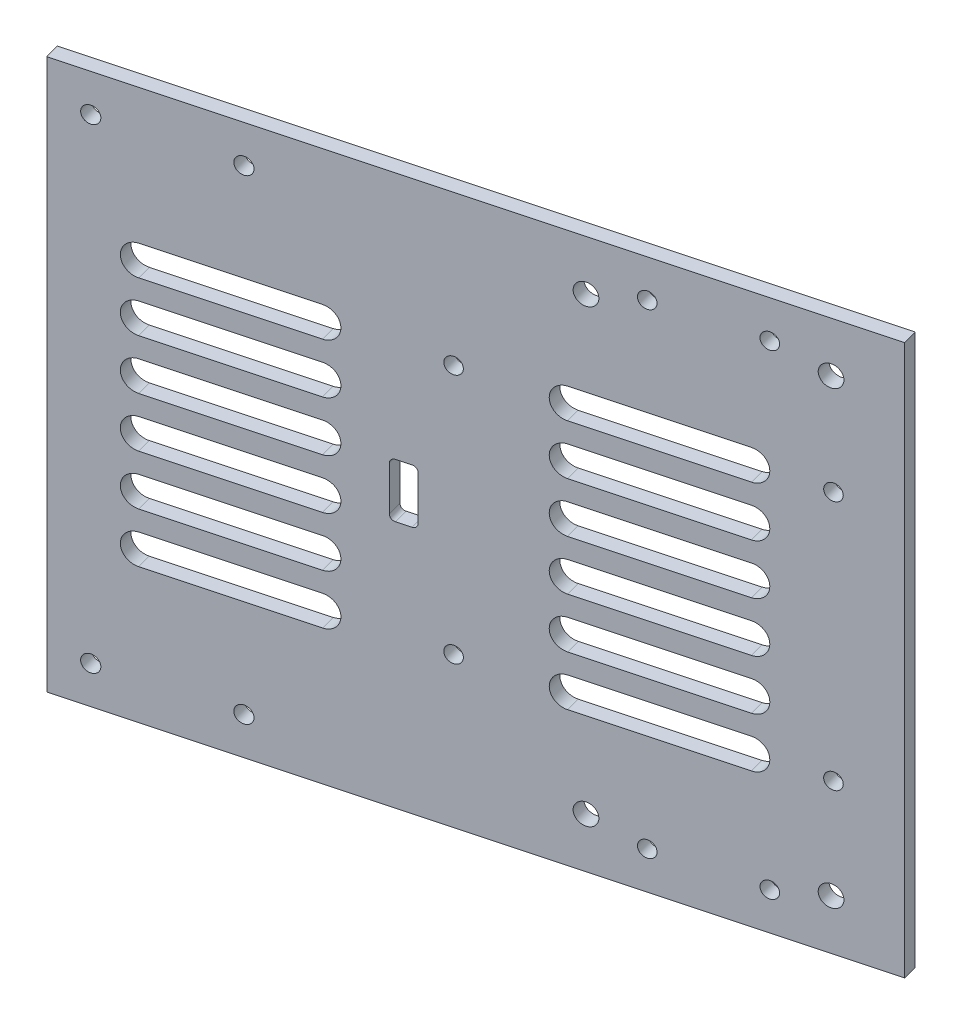
SolidWorks part; units mm, degrees
ref_plane "前视基准面" through (0, 0, 0) normal (0, 0, 1) x (1, 0, 0)
ref_plane "上视基准面" through (0, 0, 0) normal (0, 1, 0) x (1, 0, 0)
ref_plane "右视基准面" through (0, 0, 0) normal (1, 0, 0) x (0, 0, -1)
sketch "Sketch2" plane through (-8.5359, 0, -31.8565) normal (0.2588, 0, 0.9659) x (0.9659, 0, -0.2588)
  line L0 (48.5195, 100.0044) -> (48.5195, -9.9956)
  line L1 (48.5195, -9.9956) -> (188.5195, -9.9956)
  line L2 (188.5195, -9.9956) -> (188.5195, 100.0044)
  line L3 (188.5195, 100.0044) -> (48.5195, 100.0044)
  arc A4 (54.0432, -2.4956) -> (57.3432, -2.4956) centre (55.6932, -2.4956) ccw construction
  arc A5 (57.3432, -2.4956) -> (54.0432, -2.4956) centre (55.6932, -2.4956) ccw construction
  arc A6 (79.0432, -2.4956) -> (82.3432, -2.4956) centre (80.6932, -2.4956) ccw construction
  arc A7 (82.3432, -2.4956) -> (79.0432, -2.4956) centre (80.6932, -2.4956) ccw construction
  arc A8 (79.0432, 92.5044) -> (82.3432, 92.5044) centre (80.6932, 92.5044) ccw construction
  arc A9 (82.3432, 92.5044) -> (79.0432, 92.5044) centre (80.6932, 92.5044) ccw construction
  arc A10 (54.0432, 92.5044) -> (57.3432, 92.5044) centre (55.6932, 92.5044) ccw construction
  arc A11 (57.3432, 92.5044) -> (54.0432, 92.5044) centre (55.6932, 92.5044) ccw construction
  arc A12 (54.0432, -2.4956) -> (57.3432, -2.4956) centre (55.6932, -2.4956) ccw
  arc A13 (57.3432, -2.4956) -> (54.0432, -2.4956) centre (55.6932, -2.4956) ccw
  arc A14 (79.0432, -2.4956) -> (82.3432, -2.4956) centre (80.6932, -2.4956) ccw
  arc A15 (82.3432, -2.4956) -> (79.0432, -2.4956) centre (80.6932, -2.4956) ccw
  arc A16 (79.0432, 92.5044) -> (82.3432, 92.5044) centre (80.6932, 92.5044) ccw
  arc A17 (82.3432, 92.5044) -> (79.0432, 92.5044) centre (80.6932, 92.5044) ccw
  arc A18 (54.0432, 92.5044) -> (57.3432, 92.5044) centre (55.6932, 92.5044) ccw
  arc A19 (57.3432, 92.5044) -> (54.0432, 92.5044) centre (55.6932, 92.5044) ccw
  circle A20 centre (166.5195, 92.5044) radius 1.6 construction
  circle A21 centre (146.5195, 92.5044) radius 1.6 construction
  circle A22 centre (146.5195, -2.4956) radius 1.6 construction
  circle A23 centre (166.5195, -2.4956) radius 1.6 construction
  circle A24 centre (176.5195, 0.0044) radius 2.1 construction
  circle A25 centre (136.5195, 0.0044) radius 2.1 construction
  circle A26 centre (176.5195, 90.0044) radius 2.1 construction
  circle A27 centre (136.5195, 90.0044) radius 2.1 construction
  circle A28 centre (166.5195, 92.5044) radius 1.6
  circle A29 centre (146.5195, 92.5044) radius 1.6
  circle A30 centre (146.5195, -2.4956) radius 1.6
  circle A31 centre (166.5195, -2.4956) radius 1.6
  circle A32 centre (176.5195, 0.0044) radius 2.1
  circle A33 centre (136.5195, 0.0044) radius 2.1
  circle A34 centre (176.5195, 90.0044) radius 2.1
  circle A35 centre (136.5195, 90.0044) radius 2.1
  dimension "D1" = 140
extrude "Extrude1" add sketch "Sketch2" along normal blind 3
sketch "Sketch4" plane through (-7.7595, 0, -28.9587) normal (0.2588, 0, 0.9659) x (0.9659, 0, -0.2588)
  line L0 (108.1226, 50.4044) -> (105.4226, 50.4044) construction
  line L1 (104.4226, 49.4044) -> (104.4226, 40.6044) construction
  line L2 (109.1226, 40.6044) -> (109.1226, 49.4044) construction
  line L3 (105.4226, 39.6044) -> (108.1226, 39.6044) construction
  line L4 (105.4226, 39.6044) -> (108.1226, 39.6044)
  line L5 (109.1226, 40.6044) -> (109.1226, 49.4044)
  line L6 (104.4226, 49.4044) -> (104.4226, 40.6044)
  line L7 (108.1226, 50.4044) -> (105.4226, 50.4044)
  circle A0 centre (114.9099, 70.0044) radius 1.6
  circle A1 centre (176.9099, 70.0044) radius 1.6
  circle A2 centre (176.9099, 20.0044) radius 1.6
  circle A3 centre (114.9099, 20.0044) radius 1.6
  arc A4 (105.4226, 50.4044) -> (104.4226, 49.4044) centre (105.4226, 49.4044) ccw construction
  arc A5 (109.1226, 49.4044) -> (108.1226, 50.4044) centre (108.1226, 49.4044) ccw construction
  arc A6 (104.4226, 40.6044) -> (105.4226, 39.6044) centre (105.4226, 40.6044) ccw construction
  arc A7 (108.1226, 39.6044) -> (109.1226, 40.6044) centre (108.1226, 40.6044) ccw construction
  arc A8 (108.1226, 39.6044) -> (109.1226, 40.6044) centre (108.1226, 40.6044) ccw
  arc A9 (104.4226, 40.6044) -> (105.4226, 39.6044) centre (105.4226, 40.6044) ccw
  arc A10 (109.1226, 49.4044) -> (108.1226, 50.4044) centre (108.1226, 49.4044) ccw
  arc A11 (105.4226, 50.4044) -> (104.4226, 49.4044) centre (105.4226, 49.4044) ccw
  dimension "D1" = 3.2
extrude "Cut-Extrude2" cut sketch "Sketch4" against normal blind 10
sketch "Sketch5" plane through (-7.7595, 0, -28.9587) normal (0.2588, 0, 0.9659) x (0.9659, 0, -0.2588)
  line L0 (63.5195, 70.0044) -> (93.5195, 70.0044) construction
  line L1 (63.5195, 73.0044) -> (93.5195, 73.0044)
  line L2 (63.5195, 67.0044) -> (93.5195, 67.0044)
  line L3 (188.5195, 100.0044) -> (48.5195, 100.0044) construction
  line L4 (48.5195, 100.0044) -> (48.5195, -9.9956) construction
  line L5 (63.5195, 60.0044) -> (93.5195, 60.0044) construction
  line L6 (63.5195, 63.0044) -> (93.5195, 63.0044)
  line L7 (63.5195, 57.0044) -> (93.5195, 57.0044)
  line L8 (63.5195, 50.0044) -> (93.5195, 50.0044) construction
  line L9 (63.5195, 53.0044) -> (93.5195, 53.0044)
  line L10 (63.5195, 47.0044) -> (93.5195, 47.0044)
  line L11 (63.5195, 40.0044) -> (93.5195, 40.0044) construction
  line L12 (63.5195, 43.0044) -> (93.5195, 43.0044)
  line L13 (63.5195, 37.0044) -> (93.5195, 37.0044)
  line L14 (63.5195, 30.0044) -> (93.5195, 30.0044) construction
  line L15 (63.5195, 33.0044) -> (93.5195, 33.0044)
  line L16 (63.5195, 27.0044) -> (93.5195, 27.0044)
  line L17 (63.5195, 20.0044) -> (93.5195, 20.0044) construction
  line L18 (63.5195, 23.0044) -> (93.5195, 23.0044)
  line L19 (63.5195, 17.0044) -> (93.5195, 17.0044)
  line L20 (133.5195, 70.0044) -> (163.5195, 70.0044) construction
  line L21 (133.5195, 73.0044) -> (163.5195, 73.0044)
  line L22 (133.5195, 67.0044) -> (163.5195, 67.0044)
  line L23 (133.5195, 60.0044) -> (163.5195, 60.0044) construction
  line L24 (133.5195, 63.0044) -> (163.5195, 63.0044)
  line L25 (133.5195, 57.0044) -> (163.5195, 57.0044)
  line L26 (133.5195, 50.0044) -> (163.5195, 50.0044) construction
  line L27 (133.5195, 53.0044) -> (163.5195, 53.0044)
  line L28 (133.5195, 47.0044) -> (163.5195, 47.0044)
  line L29 (133.5195, 40.0044) -> (163.5195, 40.0044) construction
  line L30 (133.5195, 43.0044) -> (163.5195, 43.0044)
  line L31 (133.5195, 37.0044) -> (163.5195, 37.0044)
  line L32 (133.5195, 30.0044) -> (163.5195, 30.0044) construction
  line L33 (133.5195, 33.0044) -> (163.5195, 33.0044)
  line L34 (133.5195, 27.0044) -> (163.5195, 27.0044)
  line L35 (133.5195, 20.0044) -> (163.5195, 20.0044) construction
  line L36 (133.5195, 23.0044) -> (163.5195, 23.0044)
  line L37 (133.5195, 17.0044) -> (163.5195, 17.0044)
  arc A0 (63.5195, 73.0044) -> (63.5195, 67.0044) centre (63.5195, 70.0044) ccw
  arc A1 (93.5195, 67.0044) -> (93.5195, 73.0044) centre (93.5195, 70.0044) ccw
  arc A2 (63.5195, 63.0044) -> (63.5195, 57.0044) centre (63.5195, 60.0044) ccw
  arc A3 (93.5195, 57.0044) -> (93.5195, 63.0044) centre (93.5195, 60.0044) ccw
  arc A4 (63.5195, 53.0044) -> (63.5195, 47.0044) centre (63.5195, 50.0044) ccw
  arc A5 (93.5195, 47.0044) -> (93.5195, 53.0044) centre (93.5195, 50.0044) ccw
  arc A6 (63.5195, 43.0044) -> (63.5195, 37.0044) centre (63.5195, 40.0044) ccw
  arc A7 (93.5195, 37.0044) -> (93.5195, 43.0044) centre (93.5195, 40.0044) ccw
  arc A8 (63.5195, 33.0044) -> (63.5195, 27.0044) centre (63.5195, 30.0044) ccw
  arc A9 (93.5195, 27.0044) -> (93.5195, 33.0044) centre (93.5195, 30.0044) ccw
  arc A10 (63.5195, 23.0044) -> (63.5195, 17.0044) centre (63.5195, 20.0044) ccw
  arc A11 (93.5195, 17.0044) -> (93.5195, 23.0044) centre (93.5195, 20.0044) ccw
  arc A12 (133.5195, 73.0044) -> (133.5195, 67.0044) centre (133.5195, 70.0044) ccw
  arc A13 (163.5195, 67.0044) -> (163.5195, 73.0044) centre (163.5195, 70.0044) ccw
  arc A14 (133.5195, 63.0044) -> (133.5195, 57.0044) centre (133.5195, 60.0044) ccw
  arc A15 (163.5195, 57.0044) -> (163.5195, 63.0044) centre (163.5195, 60.0044) ccw
  arc A16 (133.5195, 53.0044) -> (133.5195, 47.0044) centre (133.5195, 50.0044) ccw
  arc A17 (163.5195, 47.0044) -> (163.5195, 53.0044) centre (163.5195, 50.0044) ccw
  arc A18 (133.5195, 43.0044) -> (133.5195, 37.0044) centre (133.5195, 40.0044) ccw
  arc A19 (163.5195, 37.0044) -> (163.5195, 43.0044) centre (163.5195, 40.0044) ccw
  arc A20 (133.5195, 33.0044) -> (133.5195, 27.0044) centre (133.5195, 30.0044) ccw
  arc A21 (163.5195, 27.0044) -> (163.5195, 33.0044) centre (163.5195, 30.0044) ccw
  arc A22 (133.5195, 23.0044) -> (133.5195, 17.0044) centre (133.5195, 20.0044) ccw
  arc A23 (163.5195, 17.0044) -> (163.5195, 23.0044) centre (163.5195, 20.0044) ccw
  point P2 (78.5195, 70.0044)
  point P14 (78.5195, 60.0044)
  point P21 (78.5195, 50.0044)
  point P28 (78.5195, 40.0044)
  point P35 (78.5195, 30.0044)
  point P42 (78.5195, 20.0044)
  point P49 (148.5195, 70.0044)
  point P56 (148.5195, 60.0044)
  point P63 (148.5195, 50.0044)
  point P70 (148.5195, 40.0044)
  point P77 (148.5195, 30.0044)
  point P84 (148.5195, 20.0044)
  dimension "D2" = 3
  dimension "D1" = 30
  dimension "D3" = 30
  dimension "D4" = 30
  dimension "D5" = 6
  dimension "D6" = 2
extrude "Extrude2" cut sketch "Sketch5" against normal blind 10
